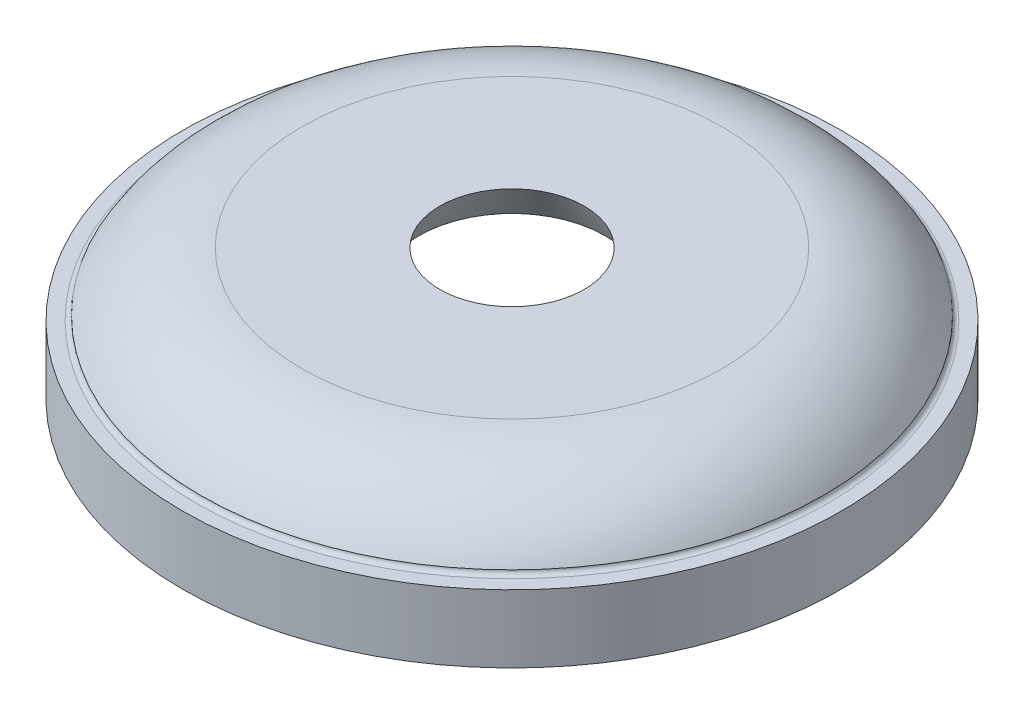
SolidWorks part; units mm, degrees
material "Silica Phenolic"
ref_plane "Piano frontale" through (0, 0, 0) normal (0, 0, 1) x (1, 0, 0)
ref_plane "Piano superiore" through (0, 0, 0) normal (0, 1, 0) x (1, 0, 0)
ref_plane "Piano destro" through (0, 0, 0) normal (1, 0, 0) x (0, 0, -1)
sketch "Schizzo1" plane through (0, 0, 0) normal (0, 0, 1) x (1, 0, 0)
  line L0 (-71, 0) -> (-73, 0)
  line L1 (-73, 0) -> (-73, 15)
  line L2 (-71, 0) -> (-71, 3)
  line L3 (-71, 3) -> (-69, 3)
  line L4 (-46.4833, 21) -> (-20.6188, 21)
  line L5 (-20.6188, 21) -> (-16, 29)
  line L6 (-16, 29) -> (-46.4833, 29)
  line L7 (0, 0) -> (0, 32.2434) construction
  line L9 (-73, 15) -> (-69, 15)
  line L10 (-69, 15) -> (-69, 16)
  line L11 (-46.4833, 21) -> (-46.4833, 29) construction
  line L13 (69, 16) -> (-69, 16) construction
  line L14 (-69, 3) -> (-68.0743, 5.6575)
  arc A3 (-69, 16) -> (-46.4833, 29) centre (-46.4833, 3) cw
  arc A5 (-54.25, 27.8129) -> (-69, 16) centre (-46.4833, 3) ccw construction
  arc A6 (-68.0743, 5.6575) -> (-46.4833, 21) centre (-46.4833, -1.8633) cw
  dimension "D3" = 3
  dimension "D4" = 30
  dimension "D1" = 8
  dimension "D2" = 4
  dimension "D5" = 146
  dimension "D6" = 32
  dimension "D7" = 29
  dimension "D8" = 15
revolve "Rivoluzione1" add sketch "Schizzo1" angle 360 about L7
fillet "Raccordo1" radius 1 1 edges at (0, 15, -69)
